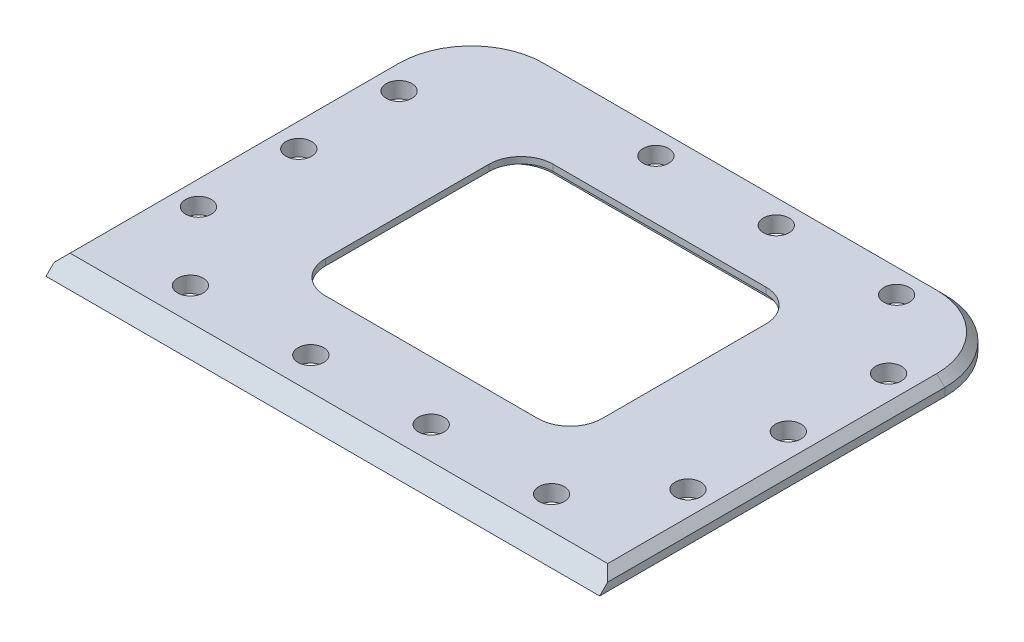
SolidWorks part; units mm, degrees
ref_plane "前视基准面" through (0, 0, 0) normal (0, 0, 1) x (1, 0, 0)
ref_plane "上视基准面" through (0, 0, 0) normal (0, 1, 0) x (1, 0, 0)
ref_plane "右视基准面" through (0, 0, 0) normal (1, 0, 0) x (0, 0, -1)
other "Configuration Table"
sketch "草图1" plane through (0, 0, 0) normal (0, 1, 0) x (1, 0, 0)
  line L0 (34.5, 51) -> (34.5, 0) construction
  line L1 (0, 0) -> (69, 0)
  line L2 (0, 0) -> (0, 51)
  line L3 (0, 51) -> (69, 51)
  line L4 (69, 0) -> (69, 51)
  line L5 (0, 25.5) -> (69, 25.5) construction
  line L6 (42, 47) -> (57, 47) construction
  line L8 (14.5, 41.7) -> (54, 41.7)
  line L9 (14.5, 41.7) -> (14.5, 9.3)
  line L10 (14.5, 9.3) -> (54, 9.3)
  line L11 (54, 41.7) -> (54, 9.3)
  circle A0 centre (4, 25.5) radius 1.6
  circle A1 centre (65, 25.5) radius 1.6
  circle A2 centre (27, 47) radius 1.6
  circle A3 centre (42, 47) radius 1.6
  circle A4 centre (42, 4) radius 1.6
  circle A5 centre (27, 4) radius 1.6
  circle A6 centre (4, 38) radius 1.6
  circle A7 centre (4, 13) radius 1.6
  circle A8 centre (65, 13) radius 1.6
  circle A9 centre (65, 38) radius 1.6
  circle A10 centre (57, 47) radius 1.6
  circle A11 centre (57, 4) radius 1.6
  circle A12 centre (12, 4) radius 1.6
  dimension "D1" = 3.2
  dimension "D2" = 61
  dimension "D3" = 15
  dimension "D4" = 43
  dimension "D7" = 25
  dimension "D8" = 15
  dimension "D9" = 10.5
  dimension "D10" = 5.3
  dimension "D5" = 69
  dimension "D6" = 51
  dimension "D11" = 11
  dimension "D12" = 5.3
extrude "凸台-拉伸1" add sketch "草图1" along normal blind 2
fillet "圆角1" radius 10 2 edges at (69, 1, -51) (0, 1, -51)
fillet "圆角2" radius 5 4 edges at (14.5, 1, -9.3) (54, 1, -9.3) (54, 1, -41.7) (14.5, 1, -41.7)
sketch "草图2" plane through (0, 2, 0) normal (0, 1, 0) x (1, 0, 0)
  line L0 (14.5, 36.7) -> (14.5, 14.3) construction
  line L1 (21.5, 39.7) -> (48, 39.7)
  line L2 (17.5, 35.7) -> (17.5, 15.3)
  line L3 (21.5, 11.3) -> (48, 11.3)
  line L4 (52, 35.7) -> (52, 15.3)
  line L5 (54, 14.3) -> (54, 36.7) construction
  line L6 (49, 41.7) -> (19.5, 41.7) construction
  line L7 (19.5, 9.3) -> (49, 9.3) construction
  line L8 (54, 14.3) -> (54, 36.7)
  line L9 (19.5, 9.3) -> (49, 9.3)
  line L10 (14.5, 36.7) -> (14.5, 14.3)
  line L11 (49, 41.7) -> (19.5, 41.7)
  arc A0 (48, 39.7) -> (52, 35.7) centre (48, 35.7) cw
  arc A1 (52, 15.3) -> (48, 11.3) centre (48, 15.3) cw
  arc A2 (21.5, 11.3) -> (17.5, 15.3) centre (21.5, 15.3) cw
  arc A3 (17.5, 35.7) -> (21.5, 39.7) centre (21.5, 35.7) cw
  arc A4 (49, 9.3) -> (54, 14.3) centre (49, 14.3) ccw construction
  arc A5 (14.5, 14.3) -> (19.5, 9.3) centre (19.5, 14.3) ccw construction
  arc A6 (19.5, 41.7) -> (14.5, 36.7) centre (19.5, 36.7) ccw construction
  arc A7 (49, 9.3) -> (54, 14.3) centre (49, 14.3) ccw
  arc A8 (14.5, 14.3) -> (19.5, 9.3) centre (19.5, 14.3) ccw
  arc A9 (19.5, 41.7) -> (14.5, 36.7) centre (19.5, 36.7) ccw
  arc A10 (54, 36.7) -> (49, 41.7) centre (49, 36.7) ccw construction
  arc A11 (54, 36.7) -> (49, 41.7) centre (49, 36.7) ccw
  dimension "D5" = 4
  dimension "D1" = 3
  dimension "D2" = 2
  dimension "D3" = 2
  dimension "D4" = 2
extrude "凸台-拉伸2" add sketch "草图2" against normal blind 0.8
sketch "草图4" plane through (69, 0, 0) normal (1, 0, 0) x (0, 0, -1)
  line L0 (0, 2) -> (-2, 0)
  line L1 (-2, 0) -> (0, 0)
  line L2 (0, 0) -> (0, 2)
  dimension "D1" = 45
extrude "凸台-拉伸4" add sketch "草图4" against normal up to surface (69 mm away) up to face at (0, 1, -20.5)
chamfer "倒角1" distance 1 angle 45 5 edges at (0, 2, -20.5) (2.9289, 2, -48.0711) (34.5, 2, -51) (66.0711, 2, -48.0711) (69, 2, -20.5)
sketch "草图3" plane through (0, 0, 0) normal (0, -1, 0) x (1, 0, 0)
  line L16 (54, -14.3) -> (54, -36.7) construction
  line L17 (49, -41.7) -> (19.5, -41.7) construction
  line L18 (14.5, -36.7) -> (14.5, -14.3) construction
  line L19 (19.5, -9.3) -> (49, -9.3) construction
  line L20 (13, -14.3) -> (13, -36.7)
  line L21 (19.5, -43.2) -> (49, -43.2)
  line L22 (55.5, -36.7) -> (55.5, -14.3)
  line L23 (49, -7.8) -> (19.5, -7.8)
  line L24 (13, -14.3) -> (13, -36.7)
  line L26 (55.5, -36.7) -> (55.5, -14.3)
  line L28 (54, -36.7) -> (54, -14.3)
  line L29 (19.5, -41.7) -> (49, -41.7)
  line L30 (14.5, -14.3) -> (14.5, -36.7)
  line L31 (49, -9.3) -> (19.5, -9.3)
  line L32 (54, -36.7) -> (54, -14.3)
  line L33 (19.5, -41.7) -> (49, -41.7)
  line L34 (14.5, -14.3) -> (14.5, -36.7)
  line L35 (49, -9.3) -> (19.5, -9.3)
  line L36 (54, -14.3) -> (54, -36.7)
  line L37 (49, -41.7) -> (19.5, -41.7)
  line L38 (14.5, -36.7) -> (14.5, -14.3)
  line L39 (19.5, -9.3) -> (49, -9.3)
  line L40 (17, -8.3) -> (51.5, -8.3)
  line L41 (17, -42.7) -> (51.5, -42.7)
  arc A20 (49, -41.7) -> (54, -36.7) centre (49, -36.7) ccw construction
  arc A21 (14.5, -36.7) -> (19.5, -41.7) centre (19.5, -36.7) ccw construction
  arc A22 (19.5, -9.3) -> (14.5, -14.3) centre (19.5, -14.3) ccw construction
  arc A23 (49, -41.7) -> (54, -36.7) centre (49, -36.7) ccw
  arc A24 (13, -36.7) -> (19.5, -43.2) centre (19.5, -36.7) ccw
  arc A25 (49, -43.2) -> (55.5, -36.7) centre (49, -36.7) ccw
  arc A26 (55.5, -14.3) -> (49, -7.8) centre (49, -14.3) ccw
  arc A27 (19.5, -7.8) -> (13, -14.3) centre (19.5, -14.3) ccw
  arc A28 (13, -36.7) -> (17, -42.7) centre (19.5, -36.7) ccw
  arc A29 (51.5, -42.7) -> (55.5, -36.7) centre (49, -36.7) ccw
  arc A30 (55.5, -14.3) -> (51.5, -8.3) centre (49, -14.3) ccw
  arc A31 (17, -8.3) -> (13, -14.3) centre (19.5, -14.3) ccw
  arc A32 (49, -41.7) -> (54, -36.7) centre (49, -36.7) ccw
  arc A33 (14.5, -36.7) -> (19.5, -41.7) centre (19.5, -36.7) ccw
  arc A34 (19.5, -9.3) -> (14.5, -14.3) centre (19.5, -14.3) ccw
  arc A35 (54, -14.3) -> (49, -9.3) centre (49, -14.3) ccw
  arc A36 (49, -41.7) -> (54, -36.7) centre (49, -36.7) ccw
  arc A37 (14.5, -36.7) -> (19.5, -41.7) centre (19.5, -36.7) ccw
  arc A38 (19.5, -9.3) -> (14.5, -14.3) centre (19.5, -14.3) ccw
  arc A39 (54, -14.3) -> (49, -9.3) centre (49, -14.3) ccw
  arc A40 (14.5, -36.7) -> (19.5, -41.7) centre (19.5, -36.7) ccw
  arc A41 (19.5, -9.3) -> (14.5, -14.3) centre (19.5, -14.3) ccw
  line M36 (54, -14.3) -> (54, -36.7)
  arc M37 (54, -36.7) -> (49, -41.7) centre (49, -36.7) cw
  line M38 (49, -41.7) -> (19.5, -41.7)
  arc M39 (19.5, -41.7) -> (14.5, -36.7) centre (19.5, -36.7) cw
  line M40 (14.5, -36.7) -> (14.5, -14.3)
  arc M41 (14.5, -14.3) -> (19.5, -9.3) centre (19.5, -14.3) cw
  line M42 (19.5, -9.3) -> (49, -9.3)
  arc M43 (49, -9.3) -> (54, -14.3) centre (49, -14.3) cw
  dimension "D3" = 1
  dimension "D4" = 1
  dimension "D1" = 1.5
  dimension "D2" = 0
extrude "凸台-拉伸3" add sketch "草图3" along normal blind 1 contours A31 L24 A28 A29 L26 A30 M43 M36 M37 M38 M39 M40 M41 M42 region at (14.5466, 0, -10.9977)
sketch "草图5" plane through (0, 0, 0) normal (0, -1, 0) x (1, 0, 0)
  line L0 (13, -14.3) -> (13, -36.7) construction
  line L1 (13, -16.5) -> (14.5, -16.5)
  line L2 (13, -16.5) -> (13, -34.5)
  line L3 (13, -34.5) -> (14.5, -34.5)
  line L4 (14.5, -16.5) -> (14.5, -34.5)
  line L5 (14.5, -36.7) -> (14.5, -14.3) construction
  line L6 (13, -25.5) -> (54, -25.5) construction
  line L7 (54, -14.3) -> (54, -36.7) construction
  dimension "D1" = 18
extrude "切除-拉伸1" cut sketch "草图5" along normal blind 1
chamfer "倒角2" distance 1 angle 45 2 edges at (13.75, 0, -34.5) (13.75, 0, -16.5)
